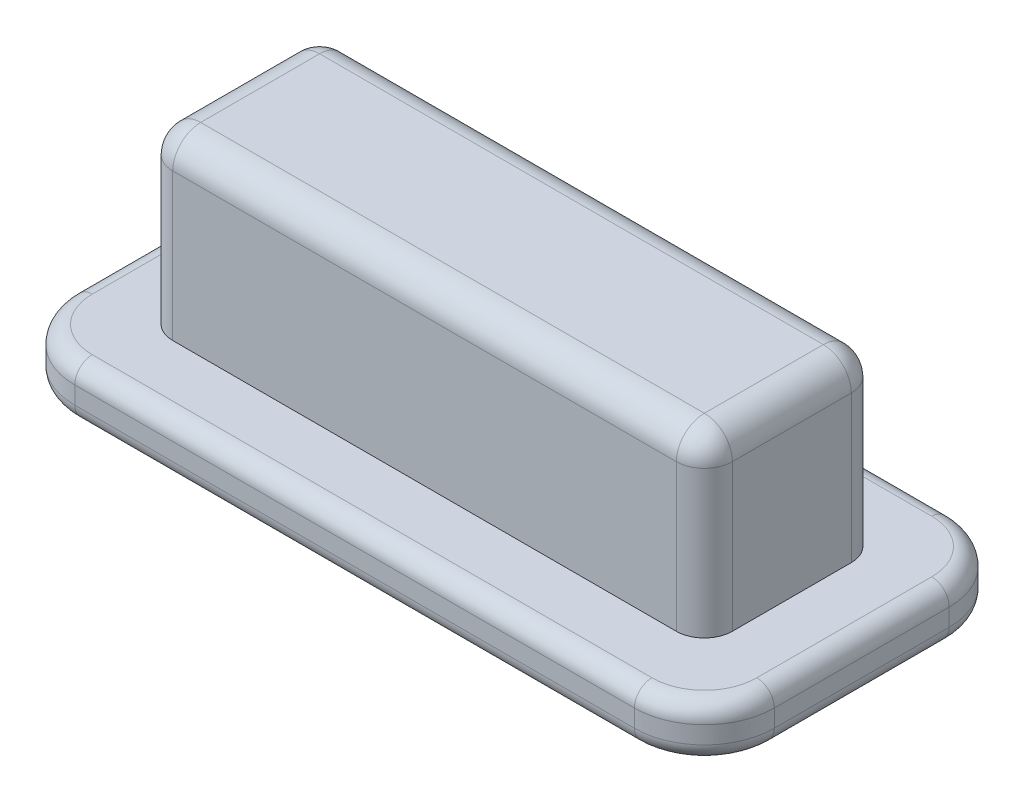
SolidWorks part; units mm, degrees
ref_plane "Front Plane" through (0, 0, 0) normal (0, 0, 1) x (1, 0, 0)
ref_plane "Top Plane" through (0, 0, 0) normal (0, 1, 0) x (1, 0, 0)
ref_plane "Right Plane" through (0, 0, 0) normal (1, 0, 0) x (0, 0, -1)
sketch "Sketch1" plane through (0, 0, 0) normal (0, 1, 0) x (1, 0, 0)
  line L1 (0, 0) -> (8, 0)
  line L2 (0, 0) -> (0, 2.5)
  line L3 (0, 2.5) -> (8, 2.5)
  line L4 (8, 0) -> (8, 2.5)
  dimension "D1" = 2.5
  dimension "D2" = 8
extrude "Boss-Extrude1" add sketch "Sketch1" along normal blind 2.5 contours L2 L1 L4 L3
sketch "Sketch2" plane through (0, 0, 0) normal (0, -1, 0) x (1, 0, 0)
  line L8 (-1, -3.5) -> (9, -3.5)
  line L9 (9, -3.5) -> (9, 1)
  line L10 (9, 1) -> (-1, 1)
  line L11 (-1, 1) -> (-1, -3.5)
  line L12 (-1, -3.5) -> (9, -3.5)
  line L13 (9, -3.5) -> (9, 1)
  line L14 (9, 1) -> (-1, 1)
  line L15 (-1, 1) -> (-1, -3.5)
  dimension "D1" = 1
extrude "Boss-Extrude2" add sketch "Sketch2" along normal blind 0.75
fillet "Fillet1" radius 0.4 4 edges at (8, 1.25, 0) (8, 1.25, -2.5) (0, 1.25, -2.5) (0, 1.25, 0)
fillet "Fillet2" radius 0.4 8 edges at (0.1172, 2.5, -0.1172) (0, 2.5, -1.25) (0.1172, 2.5, -2.3828) (4, 2.5, -2.5) (7.8828, 2.5, -2.3828) (8, 2.5, -1.25) (7.8828, 2.5, -0.1172) (4, 2.5, 0)
fillet "Fillet3" radius 1 4 edges at (9, -0.375, -3.5) (-1, -0.375, -3.5) (-1, -0.375, 1) (9, -0.375, 1)
fillet "Fillet4" radius 0.25 16 edges at (8.7071, -0.75, 0.7071) (9, -0.75, -1.25) (8.7071, -0.75, -3.2071) (4, -0.75, -3.5) (-0.7071, -0.75, -3.2071) (-1, -0.75, -1.25) (-0.7071, -0.75, 0.7071) (8.7071, 0, 0.7071) (9, 0, -1.25) (8.7071, 0, -3.2071) (4, 0, -3.5) (-0.7071, 0, -3.2071) (-1, 0, -1.25) (-0.7071, 0, 0.7071) (4, -0.75, 1) (4, 0, 1)
